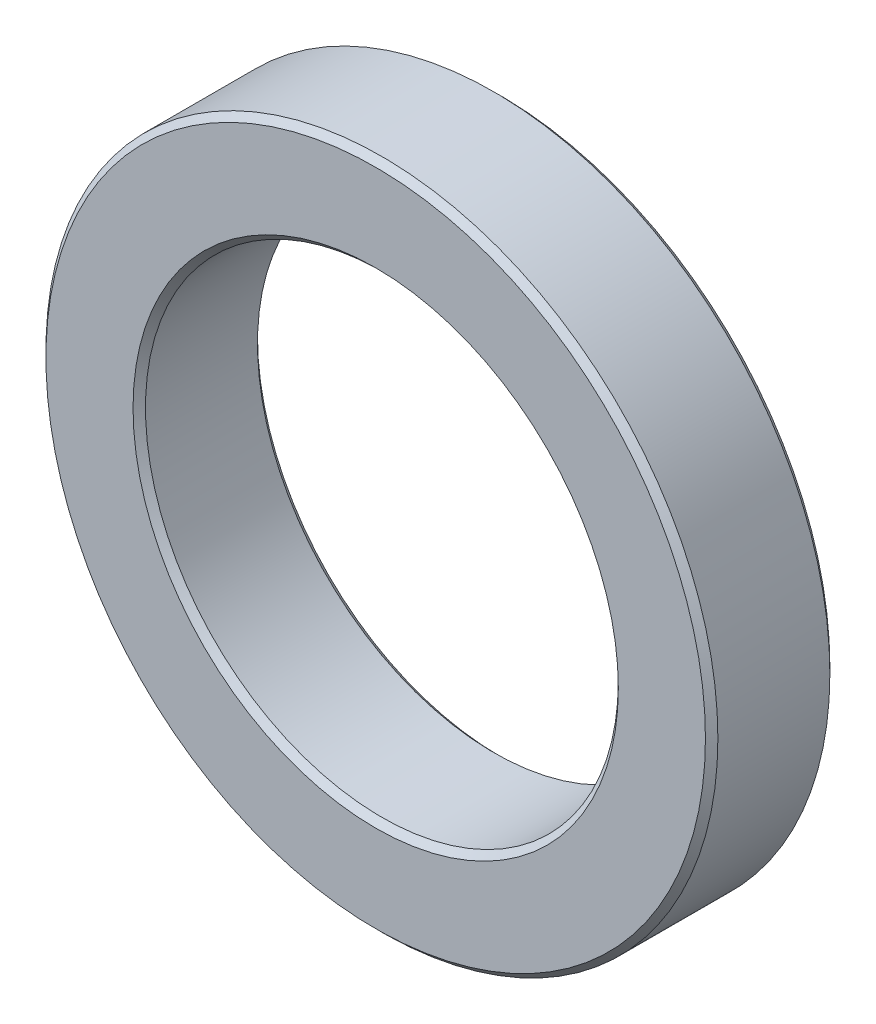
SolidWorks part; units mm, degrees
ref_plane "Ebene vorne" through (0, 0, 0) normal (0, 0, 1) x (1, 0, 0)
ref_plane "Ebene oben" through (0, 0, 0) normal (0, 1, 0) x (1, 0, 0)
ref_plane "Ebene rechts" through (0, 0, 0) normal (1, 0, 0) x (0, 0, -1)
ref_axis "Achse1" through (0, 0, -88.99) along (0, 0, 1)
sketch "Skizze1" plane through (0, 0, 0) normal (0, 0, 1) x (1, 0, 0)
  circle A0 centre (0, 0) radius 19
  circle A1 centre (0, 0) radius 27
  dimension "D1" = 54
  dimension "D2" = 38
extrude "Aufsatz-Linear austragen1" add sketch "Skizze1" along normal mid plane 10
chamfer "Fase1" distance 0.5 angle 45 4 edges at (19, 0, -5) (27, 0, -5) (27, 0, 5) (19, 0, 5)
